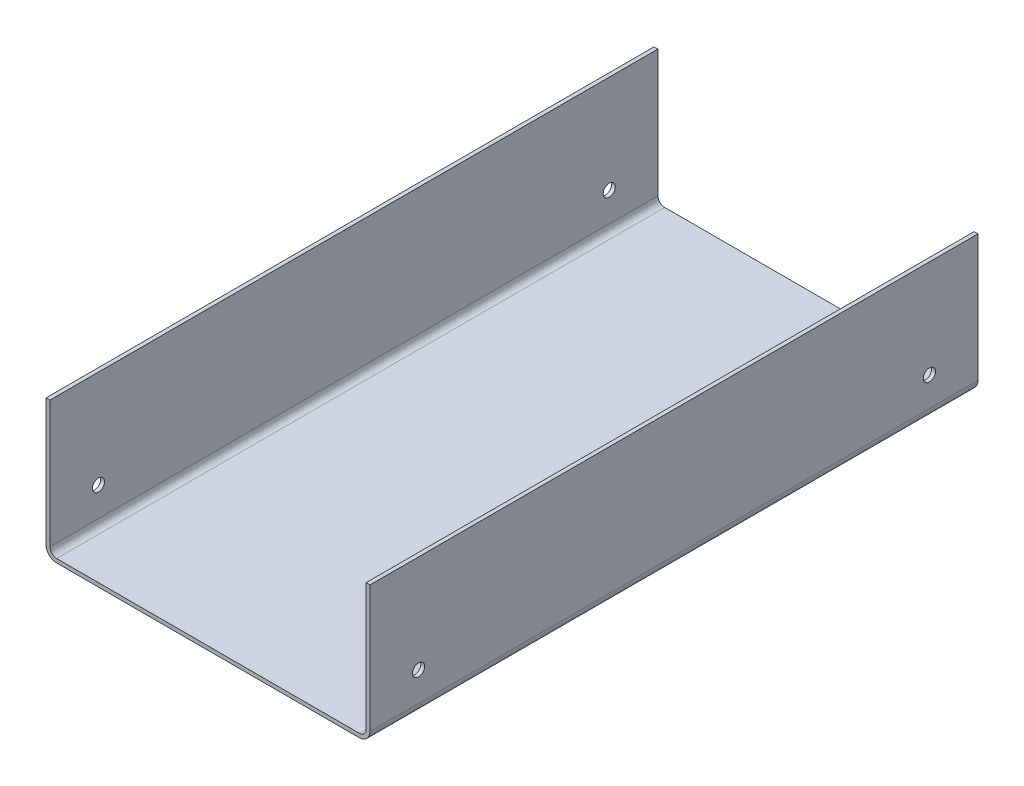
SolidWorks part; units mm, degrees
material "5052-H32"
ref_plane "Front Plane" through (0, 0, 0) normal (0, 0, 1) x (1, 0, 0)
ref_plane "Top Plane" through (0, 0, 0) normal (0, 1, 0) x (1, 0, 0)
ref_plane "Right Plane" through (0, 0, 0) normal (1, 0, 0) x (0, 0, -1)
sketch "Sketch1" plane through (0, 0, 0) normal (0, 0, 1) x (1, 0, 0)
  line L8 (130, 110) -> (130, 0)
  line L9 (-130, 0) -> (130, 0)
  line L10 (-130, 0) -> (-130, 110)
  line L11 (133.18, 110) -> (133.18, -3.18)
  line L12 (-133.18, -3.18) -> (133.18, -3.18)
  line L13 (-133.18, -3.18) -> (-133.18, 110)
  line L14 (130, 110) -> (133.18, 110)
  line L15 (-130, 110) -> (-133.18, 110)
  point P5 (0, 0)
  dimension "D2" = 110
  dimension "D4" = 110
  dimension "D3" = 260
  dimension "D1" = 3.18
extrude "Boss-Extrude1" add sketch "Sketch1" along normal blind 500
fillet "Fillet2" radius 5.5563 2 edges at (130, 0, 250) (-130, 0, 250)
fillet "Fillet3" radius 8.73 2 edges at (-133.18, -3.18, 250) (133.18, -3.18, 250)
sketch "Sketch2" plane through (133.18, 0, 0) normal (1, 0, 0) x (0, 0, -1)
  line L0 (-500, 5.55) -> (-500, 110) construction
  line L4 (-460, 29.5) -> (-460, 0) construction
  line L6 (0, 5.55) -> (0, 110) construction
  line L7 (-40, 29.5) -> (-40, 0) construction
  circle A0 centre (-460, 29.5) radius 5
  circle A1 centre (-40, 29.5) radius 5
  dimension "D3" = 10
  dimension "D4" = 10
  dimension "D1" = 40
  dimension "D2" = 29.5
  dimension "D5" = 40
  dimension "D6" = 29.5
extrude "Cut-Extrude1" cut sketch "Sketch2" against normal up to surface (266.36 mm away) up to face at (-133.18, 57.775, 250)
equation "\"L\"= 500"
equation "\"W\"= 260"
equation "\"H\"= 110"
equation "\"Compartment Width\"= 90"
equation "\"T\"= 4.7625 * 2 / 3"
equation "\"D2@Sketch1\"= \"H\""
equation "\"D4@Sketch1\"= \"H\""
equation "\"D1@Boss-Extrude1\"= \"L\""
equation "\"D1@Sketch1\"=\"T\""
equation "\"Inside Fillet Radius\"= 5.55625"
equation "\"Wheel to Wall\"= 40"
equation "\"D1@Fillet2\"=\"Inside Fillet Radius\""
equation "\"Offset\"= 20"
equation "\"Hole\"=15"
equation "\"D3@Sketch1\"=\"W\""
